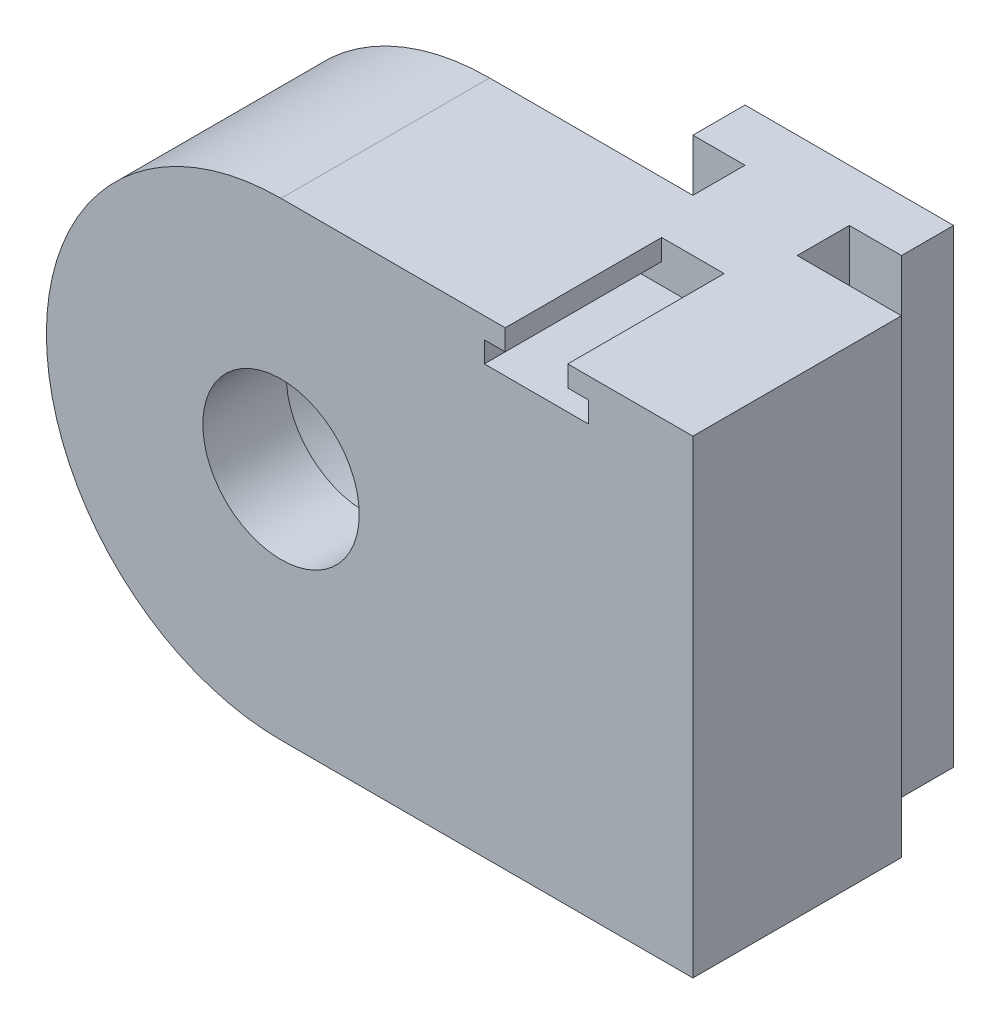
SolidWorks part; units mm, degrees
ref_plane "Plan de face" through (0, 0, 0) normal (0, 0, 1) x (1, 0, 0)
ref_plane "Plan de dessus" through (0, 0, 0) normal (0, 1, 0) x (1, 0, 0)
ref_plane "Plan de droite" through (0, 0, 0) normal (1, 0, 0) x (0, 0, -1)
sketch "Esquisse1" plane through (0, 0, 0) normal (0, 0, 1) x (1, 0, 0)
  line L0 (-634.5081, 20.5) -> (-595.0087, 20.5)
  line L1 (-595.0087, 20.5) -> (-595.0087, -24.5)
  line L2 (-595.0087, -24.5) -> (-634.5081, -24.5)
  line L3 (-666.113, -2) -> (-573.9627, -2) construction
  line L4 (-613.0087, 20.5) -> (-613.0087, 18.5)
  line L5 (-595.0087, -2) -> (-612.0087, -2)
  line L6 (-595.0087, -2) -> (-595.0087, 3.5)
  line L7 (-595.0087, 3.5) -> (-612.0087, 3.5)
  line L8 (-612.0087, -2) -> (-612.0087, 3.5)
  line L9 (-613.0087, 18.5) -> (-615.0087, 18.5)
  line L10 (-615.0087, 18.5) -> (-615.0087, 16.5)
  line L11 (-615.0087, 16.5) -> (-605.0087, 16.5)
  line L12 (-605.0087, 16.5) -> (-605.0087, 18.5)
  line L13 (-605.0087, 18.5) -> (-607.0087, 18.5)
  line L14 (-607.0087, 18.5) -> (-607.0087, 20.5)
  circle A0 centre (-634.5081, -2) radius 7.5
  arc A1 (-634.5081, 20.5) -> (-634.5081, -24.5) centre (-634.5081, -2) ccw
  circle A3 centre (-606.8206, -19) radius 4
  circle A5 centre (-634.5081, -2) radius 14
  circle A7 centre (-604.0087, 3.5) radius 2
  point P6 (-610.0087, 16.5)
  dimension "D1" = 5.5
  dimension "D3" = 2
  dimension "D4" = 17
  dimension "D5" = 28
  dimension "D6" = 15
  dimension "D8" = 8
  dimension "D9" = 15
  dimension "D11" = 4
  dimension "D12" = 8
  dimension "D13" = 6
  dimension "D2" = 17
  dimension "D7" = 45
  dimension "D10" = 39.4994
  dimension "D14" = 10
  dimension "D15" = 2
extrude "Boss.-Extru.1" add sketch "Esquisse1" along normal mid plane 20 contours L1 L2 A1 L0 | A0
extrude "Enlèv. mat.-Extru.1" cut sketch "Esquisse1<5>" against normal blind 10 and the other way blind 2 contours A5
sketch "Esquisse1<5>" plane through (0, 0, 0) normal (0, 0, 1) x (1, 0, 0) same geometry as "Esquisse1"
sketch "Esquisse2" plane through (0, 20.5, 0) normal (0, 1, 0) x (1, 0, 0)
  line L0 (-605.0087, 10) -> (-605.0087, 15)
  line L1 (-634.5081, 10) -> (-595.0087, 10) construction
  line L2 (-605.0087, 15) -> (-600.0087, 15)
  line L3 (-600.0087, 15) -> (-600.0087, 20)
  line L4 (-600.0087, 20) -> (-620.0087, 20)
  line L5 (-620.0087, 20) -> (-620.0087, 15)
  line L6 (-620.0087, 15) -> (-615.0087, 15)
  line L7 (-615.0087, 15) -> (-615.0087, 10)
  line L8 (-615.0087, 10) -> (-605.0087, 10)
  line L10 (-595.0087, -10) -> (-595.0087, 10) construction
  dimension "D1" = 20
  dimension "D2" = 5
  dimension "D3" = 10
  dimension "D4" = 10
  dimension "D5" = 5
extrude "Boss.-Extru.2" add sketch "Esquisse2" against normal blind 45
extrude "Enlèv. mat.-Extru.2" cut sketch "Esquisse1<7>" along normal through all and the other way blind 5 contours L13 L14 L0 L4 L9 L10 L11 L12 region at (-610.0087, 18.25, 0)
sketch "Esquisse1<7>" plane through (0, 0, 0) normal (0, 0, 1) x (1, 0, 0) same geometry as "Esquisse1"
